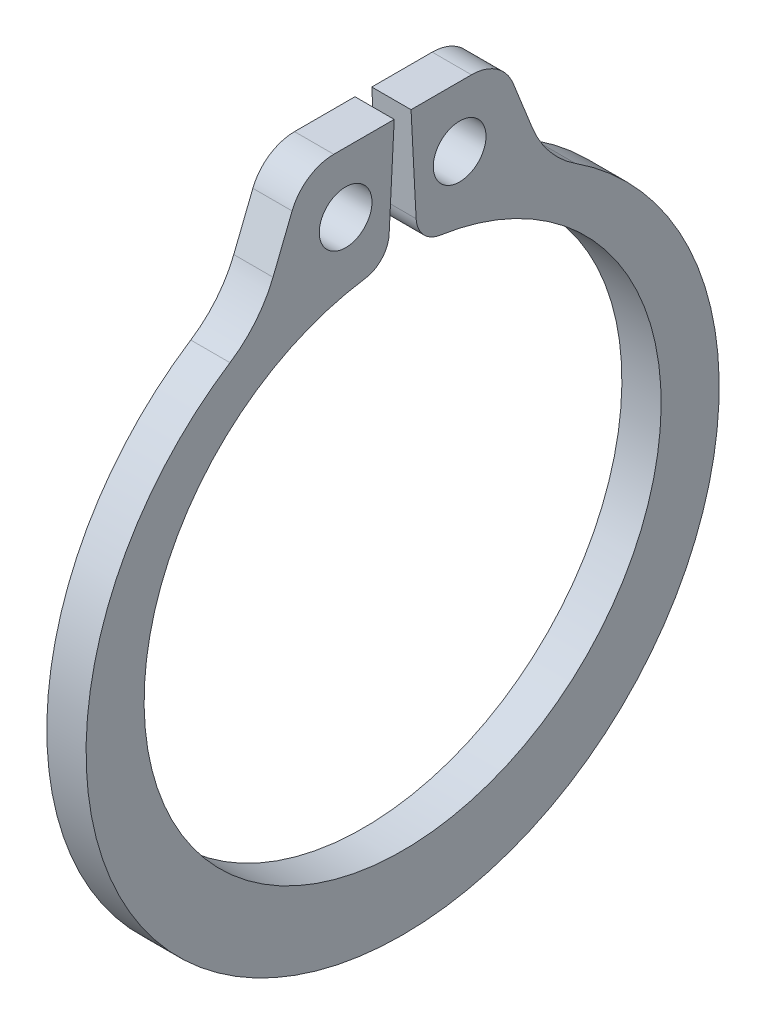
SolidWorks part; units mm, degrees
material "Cast Carbon Steel"
ref_plane "Front" through (0, 0, 0) normal (0, 0, 1) x (1, 0, 0)
ref_plane "Top" through (0, 0, 0) normal (0, 1, 0) x (1, 0, 0)
ref_plane "Right" through (0, 0, 0) normal (1, 0, 0) x (0, 0, -1)
sketch "Sketch1" plane through (0, 0, 0) normal (1, 0, 0) x (0, 0, -1)
  line L0 (0, 0) -> (0, 5.8547) construction
  line L2 (0.1905, 8.5846) -> (2.2479, 8.5846)
  line L3 (2.2479, 8.5846) -> (3.2587, 6.0487)
  line L5 (-0.1905, 8.5846) -> (-2.2479, 8.5846)
  line L6 (-2.2479, 8.5846) -> (-3.2587, 6.0487)
  line L7 (-3.2587, 6.0487) -> (-2.7768, 5.1543) construction
  line L8 (3.2587, 6.0487) -> (2.7768, 5.1543) construction
  line L9 (0, -5.8547) -> (0, -7.5057) construction
  line L10 (-2.2479, 8.5846) -> (-0.3341, 5.8452) construction
  line L11 (0, 5.8547) -> (0, 8.5846) construction
  line L12 (-5.8547, 0) -> (5.8547, 0) construction
  line L13 (-0.1905, 8.5846) -> (-0.3341, 5.8452) construction
  line L14 (0.1905, 8.5846) -> (0.3341, 5.8452) construction
  circle A0 centre (0, 0) radius 5.8547 construction
  arc A1 (-0.3341, 5.8452) -> (0.3341, 5.8452) centre (0, 0) ccw
  circle A4 centre (-1.291, 7.2149) radius 0.5969
  circle A5 centre (1.291, 7.2149) radius 0.5969
  arc A6 (-3.2587, 6.0487) -> (3.2587, 6.0487) centre (0, -0.3368) ccw construction
  point P0 (0, -7.5057)
  dimension "Ring ID" = 11.7094
  dimension "Hole Diameter" = 1.1938
  dimension "Min. Sec." = 1.016
  dimension "Max. Sec." = 1.651
  dimension "Lug Height" = 2.7432
  dimension "D2" = 2.0574
  dimension "Angle" = 3
  dimension "D1" = 0.381
sketch "Sketch2" plane through (0, 0, 0) normal (0, 1, 0) x (1, 0, 0)
  line L0 (-0.4445, -7.161) -> (0.4445, -7.161) construction
  line L1 (0, -7.1689) -> (0, 7.1689) construction
  point P8 (0, -7.161)
  dimension "Ring Thickness" = 0.889
sketch "Sketch3" plane through (0, 0, 0) normal (1, 0, 0) x (0, 0, -1)
  line L0 (-2.2479, 8.5846) -> (-3.2587, 6.0487) construction
  line L1 (-2.2479, 8.5846) -> (-3.2587, 6.0487)
  line L2 (-0.1905, 8.5846) -> (-2.2479, 8.5846) construction
  line L3 (-0.1905, 8.5846) -> (-2.2479, 8.5846)
  line L5 (-0.3341, 5.8452) -> (-0.1905, 8.5846)
  line L8 (0.1905, 8.5846) -> (2.2479, 8.5846) construction
  line L9 (0.1905, 8.5846) -> (2.2479, 8.5846)
  line L10 (2.2479, 8.5846) -> (3.2587, 6.0487) construction
  line L11 (2.2479, 8.5846) -> (3.2587, 6.0487)
  line L12 (0.1905, 8.5846) -> (0.3341, 5.8452) construction
  line L13 (0.1905, 8.5846) -> (0.3341, 5.8452)
  arc A0 (-3.2587, 6.0487) -> (3.2587, 6.0487) centre (0, -0.3368) ccw construction
  arc A1 (-3.2587, 6.0487) -> (3.2587, 6.0487) centre (0, -0.3368) ccw
  arc A2 (-0.3341, 5.8452) -> (0.3341, 5.8452) centre (0, 0) ccw construction
  arc A3 (-0.3341, 5.8452) -> (0.3341, 5.8452) centre (0, 0) ccw
  circle A4 centre (-1.291, 7.2149) radius 0.5969 construction
  circle A5 centre (-1.291, 7.2149) radius 0.5969
  circle A6 centre (1.291, 7.2149) radius 0.5969 construction
  circle A7 centre (1.291, 7.2149) radius 0.5969
extrude "Boss-Extrude1" add sketch "Sketch3" along normal up to vertex (0.4445 mm away) and the other way up to vertex (0.4445 mm away) up to point (0.4445, 0, 7.161) other way up to point (-0.4445, 0, 7.161)
fillet "Fillet1" radius 2.54 2 edges at (0, 6.0487, -3.2587) (0, 6.0487, 3.2587)
fillet "Fillet2" radius 0.635 2 edges at (0, 5.8452, -0.3341) (0, 5.8452, 0.3341)
fillet "Fillet3" radius 1.016 2 edges at (0, 8.5846, -2.2479) (0, 8.5846, 2.2479)
sketch "Sketch4" plane through (0, 0, 0) normal (1, 0, 0) x (0, 0, -1)
  line L0 (-5.0703, 2.9274) -> (0, 0) construction
  line L1 (0, 0) -> (0, 5.8547) construction
  line L2 (0, 8.5846) -> (0, 5.8547) construction
  arc A0 (-0.3341, 5.8452) -> (0.3341, 5.8452) centre (0, 0) ccw construction
  point P0 (0, 0)
  point P1 (-5.0703, 2.9274)
  dimension "D1" = 60
equation "\"D2@Sketch1\" = \"Lug Height@Sketch1\" * .75"
